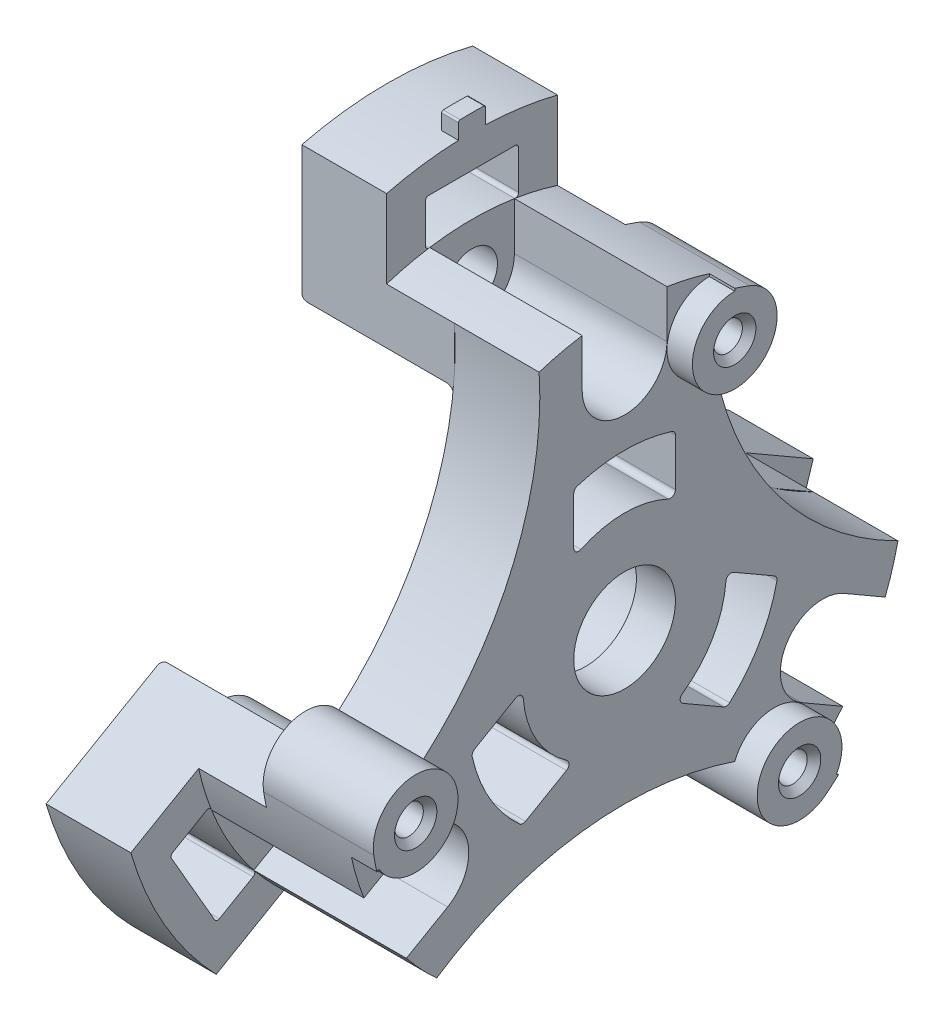
SolidWorks part; units mm, degrees
ref_plane "Front" through (0, 0, 0) normal (0, 0, 1) x (1, 0, 0)
ref_plane "Top" through (0, 0, 0) normal (0, 1, 0) x (1, 0, 0)
ref_plane "Right" through (0, 0, 0) normal (1, 0, 0) x (0, 0, -1)
sketch "草图1" plane through (0, 0, 0) normal (0, 0, 1) x (1, 0, 0)
  line L0 (-65.7429, 0) -> (89.5714, 0) construction
  line L1 (0, 67.1143) -> (0, -71.9143) construction
  line L2 (-7, 6) -> (-5, 6)
  line L3 (-5, 6) -> (-5, 16.5)
  line L4 (-5, 16.5) -> (0, 16.5)
  line L5 (0, 16.5) -> (0, 3)
  line L6 (-2.3, 3.975) -> (-7, 3.975)
  line L7 (-7, 3.975) -> (-7, 6)
  line L8 (-2.3, 3.975) -> (-2.3, 3)
  line L9 (-2.3, 3) -> (0, 3)
  dimension "D1" = 6
  dimension "D2" = 4.7
  dimension "D3" = 7.95
  dimension "D4" = 7
  dimension "D5" = 5
  dimension "D6" = 12
  dimension "D7" = 33
  dimension "D8" = 2.3
revolve "旋转1" add sketch "草图1" angle 360 about L0
sketch "草图2" plane through (-5, 0, 0) normal (-1, 0, 0) x (0, 0, 1)
  line L0 (-23.9515, 0) -> (26.381, 0) construction
  line L1 (0, 44.3891) -> (0, -20.5254) construction
  line L2 (0, 0) -> (-21.2641, -12.2768) construction
  line L3 (0, 0) -> (20.7932, -12.005) construction
  line L4 (0, 0) -> (-61.1055, 35.2793) construction
  line L5 (-5, 31.2128) -> (-5, 9) construction
  line L6 (5, 31.2128) -> (5, 9) construction
  circle A1 centre (-25, 14.4338) radius 20
  point P7 (0, 9)
  point P9 (-7.6795, 4.4338)
  dimension "D6" = 40
  dimension "D1" = 120
  dimension "D2" = 120
  dimension "D3" = 9
  dimension "D5" = 60
  dimension "D7" = 10
extrude "切除-拉伸1" cut sketch "草图2" against normal blind 10 contours A1
pattern_circular "阵列(圆周)1" count 3 over 360 about axis through (-7, 0, 0) along (-1, 0, 0) of "切除-拉伸1"
sketch "草图3" plane through (-5, 0, 0) normal (-1, 0, 0) x (0, 0, 1)
  line L0 (0, 18) -> (0, -12.9057) construction
  line L1 (-20.442, 0) -> (20.8303, 0) construction
  line L2 (-3, 8.4806) -> (-3, 5.6921)
  line L4 (3, 8.4806) -> (3, 5.6921)
  arc A0 (2.791, 8.7664) -> (-2.791, 8.7664) centre (0, 0) ccw
  circle A1 centre (0, 0) radius 6 construction
  arc A2 (2.5714, 5.421) -> (-2.5714, 5.421) centre (0, 0) ccw
  arc A3 (3, 5.6921) -> (2.5714, 5.421) centre (2.7, 5.6921) cw
  arc A4 (-2.5714, 5.421) -> (-3, 5.6921) centre (-2.7, 5.6921) cw
  arc A5 (3, 8.4806) -> (2.791, 8.7664) centre (2.7, 8.4806) ccw
  arc A6 (-2.791, 8.7664) -> (-3, 8.4806) centre (-2.7, 8.4806) ccw
  point P11 (3, 5.1962)
  point P16 (-3, 5.1962)
  point P19 (3, 8.6971)
  point P22 (-3, 8.6971)
  dimension "D1" = 9.2
  dimension "D3" = 0.3
  dimension "D2" = 6
extrude "切除-拉伸2" cut sketch "草图3" against normal blind 10
pattern_circular "阵列(圆周)2" count 3 over 360 about axis through (-2.3, 0, 0) along (-1, 0, 0) of "切除-拉伸2"
sketch "草图4" plane through (-5, 0, 0) normal (-1, 0, 0) x (0, 0, 1)
  line L0 (-16.7535, 0) -> (15.8993, 0) construction
  line L1 (0, 19.3876) -> (0, -16.6742) construction
  line L2 (-5.0408, 15.7111) -> (-5.0408, 12.4427)
  line L4 (5.0408, 12.4427) -> (5.0408, 15.7111)
  circle A0 centre (0, 0) radius 13.5 construction
  arc A1 (5.0408, 15.7111) -> (-5.0408, 15.7111) centre (0, 0) ccw construction
  arc A2 (5.0408, 15.7111) -> (-5.0408, 15.7111) centre (0, 0) ccw
  circle A3 centre (0, 13.5) radius 1.5
  arc A4 (-2.7761, 13.1348) -> (2.7761, 13.1348) centre (0, 13.5) ccw
  arc A5 (-2.7761, 13.1348) -> (-5.0408, 12.4427) centre (0, 0) ccw
  arc A6 (5.0408, 12.4427) -> (2.7761, 13.1348) centre (0, 0) ccw
  dimension "D1" = 27
  dimension "D2" = 3
  dimension "D4" = 5.6
  dimension "D5" = 26.85
extrude "凸台-拉伸1" add sketch "草图4" along normal blind 9
pattern_circular "阵列(圆周)3" count 3 over 360 about axis through (-65.7429, 0, 0) along (-1, 0, 0) of "凸台-拉伸1"
sketch "草图5" plane through (-14, 0, 0) normal (-1, 0, 0) x (0, 0, 1)
  line L0 (-16.1323, 0) -> (16.637, 0) construction
  line L1 (0, 17.8058) -> (0, -12.3621) construction
  line L3 (-2.8, 13.1298) -> (-2.8, 9.2908)
  line L4 (-2.8, 9.2908) -> (2.8, 9.2908)
  line L5 (2.8, 13.1298) -> (2.8, 9.2908)
  arc A2 (2.8, 13.1298) -> (-2.8, 13.1298) centre (0, 0) ccw
  point P10 (0, 9.2908)
  point P11 (0, 13.55)
  dimension "D1" = 5.6
  dimension "D2" = 26.85
extrude "切除-拉伸3" cut sketch "草图5" against normal blind 1.7 contours L4 L5 A2 L3
sketch "草图10" plane through (-5, 0, 0) normal (-1, 0, 0) x (0, 0, 1)
  point P1 (0, 0)
  dimension "D1" = 12.8775
pattern_circular "阵列(圆周)4" count 3 over 360 about axis through (-65.7429, 0, 0) along (-1, 0, 0) of "切除-拉伸3" reverse direction yes
sketch "草图6" plane through (0, 0, 0) normal (1, 0, 0) x (0, 0, -1)
  line L0 (-17.245, 0) -> (20.4566, 0) construction
  line L1 (0, 20.1005) -> (0, -14.3306) construction
  line L2 (-2.5, 16.3095) -> (-2.5, 13.5)
  line L3 (2.5, 16.3095) -> (2.5, 13.5)
  circle A0 centre (0, 0) radius 13.5 construction
  arc A1 (5.0408, 15.7111) -> (-5.0408, 15.7111) centre (0, 0) ccw construction
  arc A3 (2.5, 16.3095) -> (-2.5, 16.3095) centre (0, 0) ccw
  arc A4 (-2.5, 13.5) -> (2.5, 13.5) centre (0, 13.5) ccw
  dimension "D1" = 27
  dimension "D3" = 5
  dimension "D2" = 5
extrude "切除-拉伸4" cut sketch "草图6" against normal blind 9
pattern_circular "阵列(圆周)5" count 3 over 360 about axis through (-65.7429, 0, 0) along (-1, 0, 0) of "切除-拉伸4"
sketch "草图7" plane through (-5, 0, 0) normal (-1, 0, 0) x (0, 0, 1)
  line L0 (0, 19.1221) -> (0, -13.8647) construction
  line L1 (16.0973, 0) -> (-17.961, 0) construction
  line L2 (-5, 15.5767) -> (-5, 15.7242)
  arc A1 (-5.8929, 15.4118) -> (-5, 15.5767) centre (-5, 13.0767) ccw
  circle A5 centre (0, 0) radius 14 construction
  arc A6 (-2.5, 16.3095) -> (-5.0408, 15.7111) centre (0, 0) ccw construction
  arc A7 (-5, 15.7242) -> (-5.8929, 15.4118) centre (0, 0) ccw
  point P7 (-5, 13.0767)
  dimension "D1" = 28
  dimension "D3" = 5
  dimension "D2" = 5
extrude "凸台-拉伸2" add sketch "草图7" against normal blind 6.5
sketch "草图9" plane through (1.5, 0, 0) normal (1, 0, 0) x (0, 0, -1)
  line L0 (0, 17.5729) -> (0, -10.6538) construction
  line L1 (-14.0745, 0) -> (16.4041, 0) construction
  circle A0 centre (0, 0) radius 14 construction
  circle A1 centre (5, 13.0767) radius 0.85
  dimension "D1" = 1.7
extrude "切除-拉伸7" cut sketch "草图9" against normal blind 6.4 contours A1
chamfer "倒角3" distance 0.4 angle 45 1 edges at (1.5, 13.0767, -5.85)
pattern_circular "阵列(圆周)8" count 3 over 360 about axis through (-65.7429, 0, 0) along (-1, 0, 0) of "凸台-拉伸2", "切除-拉伸7", "倒角3"
chamfer "倒角4" distance 0.3 angle 60 1 edges at (-7, 0, 3.975) first distance on face at (-7, 0, 3.975)
fillet "圆角6" radius 0.5 9 edges at (-5, 12.8388, 3.9238) (-5, 12.8388, -3.9238) (-5, 10.7, 0) (-5, -3.0213, -13.0806) (-5, -5.35, -9.2665) (-5, -9.8175, -9.1569) (-5, -9.8175, 9.1569) (-5, -3.0213, 13.0806) (-5, -5.35, 9.2665)
fillet "圆角7" radius 0.5 1 edges at (-7, 0, 6)
sketch "草图11" plane through (-14, 0, 0) normal (-1, 0, 0) x (0, 0, 1)
  line L0 (-24.0343, 0) -> (27.0991, 0) construction
  line L1 (0, 23.8854) -> (0, -19.7008) construction
  line L2 (-5.0408, 15.7111) -> (-5.0408, 20.3345)
  line L3 (5.0408, 15.7111) -> (5.0408, 20.3345)
  line L4 (-2.55, 19) -> (2.55, 19)
  line L5 (-2.75, 18.8) -> (-2.75, 16.2692)
  line L7 (2.75, 18.8) -> (2.75, 16.2692)
  arc A0 (5.0408, 20.3345) -> (0, 20.95) centre (0, 0) ccw
  arc A1 (5.0408, 15.7111) -> (-5.0408, 15.7111) centre (0, 0) ccw construction
  arc A2 (5.0408, 15.7111) -> (2.75, 16.2692) centre (0, 0) ccw
  arc A3 (-2.75, 16.2692) -> (-5.0408, 15.7111) centre (0, 0) ccw
  arc A4 (0, 20.95) -> (-5.0408, 20.3345) centre (0, 0) ccw
  arc A5 (2.75, 18.8) -> (2.55, 19) centre (2.55, 18.8) ccw
  arc A6 (-2.75, 18.8) -> (-2.55, 19) centre (-2.55, 18.8) cw
  point P15 (0, 17)
  point P16 (0, 19)
  point P18 (2.75, 19)
  point P20 (0, 22)
  point P23 (-2.75, 19)
  dimension "D1" = 41.9
  dimension "D4" = 0.2
  dimension "D2" = 5.5
  dimension "D3" = 19
extrude "凸台-拉伸3" add sketch "草图11" against normal up to surface (5 mm away) up to face at (-9, 13.5, -1.5)
pattern_circular "阵列(圆周)9" count 3 over 360 about axis through (-6.4804, 0, 0) along (-1, 0, 0) of "凸台-拉伸3"
sketch "草图12" plane through (-9, 0, 0) normal (1, 0, 0) x (0, 0, -1)
  line L0 (0, 23.0537) -> (0, -15.9342) construction
  line L1 (-23.5138, 0) -> (22.1093, 0) construction
  line L2 (-0.8, 21.8388) -> (-0.8, 20.9347)
  line L3 (0.8, 21.8388) -> (0.8, 20.9347)
  arc A0 (0.7032, 21.9387) -> (-0.7032, 21.9387) centre (0, 0) ccw
  arc A1 (5.0408, 20.3345) -> (-5.0408, 20.3345) centre (0, 0) ccw construction
  arc A2 (0.8, 20.9347) -> (-0.8, 20.9347) centre (0, 0) ccw
  arc A3 (-21.95, 0) -> (21.95, 0) centre (0, 0) ccw
  arc A4 (-0.8, 21.8388) -> (-0.7032, 21.9387) centre (-0.7, 21.8388) cw
  arc A5 (0.7032, 21.9387) -> (0.8, 21.8388) centre (0.7, 21.8388) cw
  dimension "D2" = 1
  dimension "D3" = 0.1
  dimension "D1" = 1.6
extrude "凸台-拉伸4" add sketch "草图12" against normal blind 1 contours A0 A4 L2 A2 L3 A5
pattern_circular "阵列(圆周)10" [suppressed] count 3 over 360 of bodies 124
fillet "圆角9" radius 0.3 6 edges at (-14, -9.3622, -9.6218) (-14, -3.6516, -12.9188) (-14, 13.0138, -3.297) (-14, 13.0138, 3.297) (-14, -9.3622, 9.6218) (-14, -3.6516, 12.9188)
fillet "圆角10" radius 0.2 6 edges at (-11.5, -10.5162, -12.7146) (-11.5, -5.753, -15.4646) (-11.5, -10.5162, 12.7146) (-11.5, -5.753, 15.4646) (-11.5, 16.2692, 2.75) (-11.5, 16.2692, -2.75)
